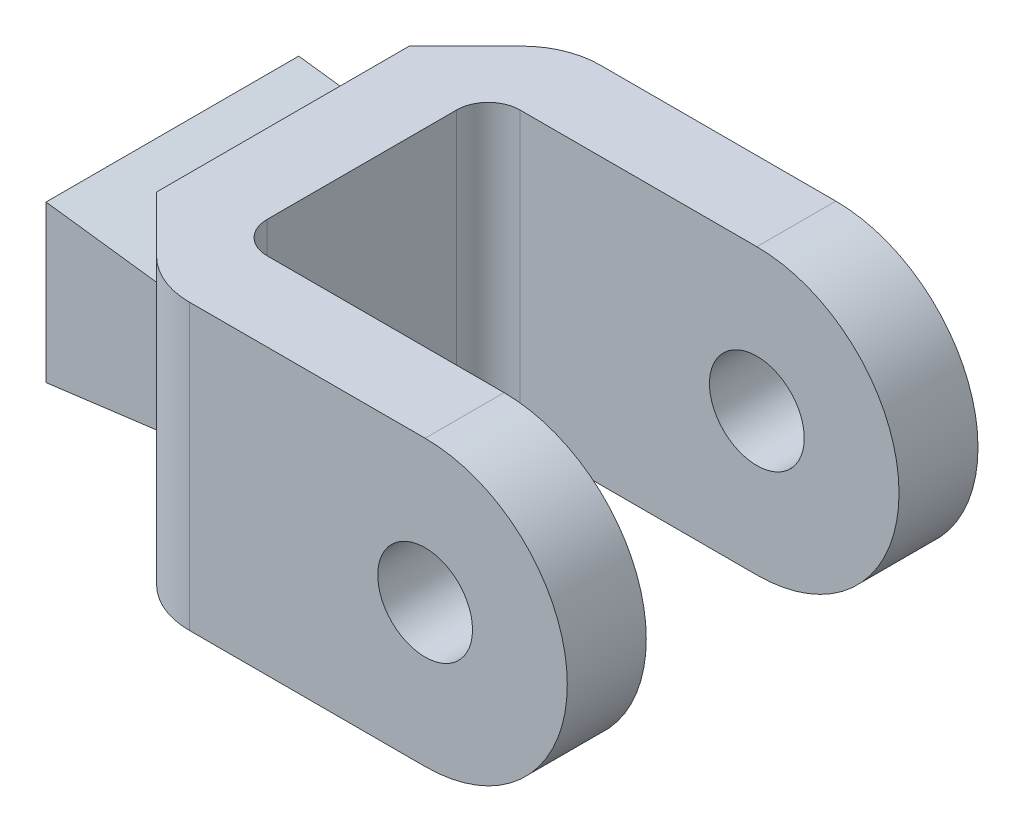
SolidWorks part; units mm, degrees
ref_plane "Front Plane" through (0, 0, 0) normal (0, 0, 1) x (1, 0, 0)
ref_plane "Top Plane" through (0, 0, 0) normal (0, 1, 0) x (1, 0, 0)
ref_plane "Right Plane" through (0, 0, 0) normal (1, 0, 0) x (0, 0, -1)
sketch "Sketch1" plane through (0, 0, 0) normal (0, 0, 1) x (1, 0, 0)
  line L0 (-2.2687, 0) -> (4.5375, 0) construction
  line L4 (-1.75, -2.475) -> (-1.75, 2.475)
  line L5 (1.4583, -2.0625) -> (-1.75, 2.475) construction
  line L6 (1.4583, 2.0625) -> (-1.75, -2.475) construction
  line L7 (-1.75, -2.475) -> (1.75, -2.025)
  line L8 (-1.75, 2.475) -> (1.75, 2.025)
  line L21 (1.75, 2.025) -> (1.75, 4.5)
  line L22 (4.25, -4.5) -> (1.75, -4.5)
  line L25 (4.25, -4.5) -> (4.25, 4.5)
  line L26 (4.25, 4.5) -> (1.75, 4.5)
  line L27 (1.75, -4.5) -> (1.75, -2.025)
  line L28 (4.25, -4.5) -> (1.75, 4.5) construction
  line L29 (4.25, 4.5) -> (1.75, -4.5) construction
  point P0 (0, 0)
  point P2 (3, 0)
  point P3 (3, 0)
  point P6 (1.75, 2.025)
  point P9 (1.75, -2.025)
  dimension "D1" = 4.95
  dimension "D2" = 2.5
  dimension "D3" = 9
extrude "Boss-Extrude1" add sketch "Sketch1" along normal blind 8 contours L8 L21 L26 L25 L22 L27 L7 L4
sketch "Sketch2" plane through (0, 0, 0) normal (0, 0, 1) x (1, 0, 0)
  line L0 (-1.75, 0) -> (25.7432, 0) construction
  line L1 (-1.75, -2.475) -> (-1.75, 2.475) construction
  line L3 (12.75, -4.5) -> (1.75, -4.5)
  line L5 (12.75, 4.5) -> (1.75, 4.5)
  line L6 (1.75, -4.5) -> (1.75, 4.5)
  line L7 (15.7356, -3.3669) -> (1.75, 4.5) construction
  line L8 (15.7356, 3.3669) -> (1.75, -4.5) construction
  line L11 (1.75, -4.5) -> (1.75, -2.025) construction
  arc A0 (12.75, -4.5) -> (12.75, 4.5) centre (12.75, 0) ccw
  circle A1 centre (12.75, 0) radius 1.5
  circle A2 centre (12.75, 0) radius 7.5 construction
  point P5 (9.75, 0)
  point P7 (17.25, 0)
  dimension "D3" = 3
  dimension "D4" = 15
  dimension "D1" = 15.5
  dimension "D2" = 9
extrude "Boss-Extrude3" add sketch "Sketch2" against normal blind 2.5
sketch "Sketch5" plane through (0, 0, 0) normal (0, 1, 0) x (1, 0, 0)
  line L0 (4.25, 0) -> (4.25, 4.091) construction
  line L1 (12.75, 2.5) -> (1.75, 2.5) construction
  line L2 (1.75, 0) -> (4.25, 2.5)
  line L3 (4.25, 2.5) -> (1.75, 2.5)
  line L4 (1.75, 2.5) -> (1.75, 0)
  point P3 (4.25, 2.5)
extrude "Cut-Extrude2" cut sketch "Sketch5" against normal through all and the other way through all
fillet "Fillet5" radius 1 1 edges at (4.25, 0, 0)
fillet "Fillet6" radius 2.5 1 edges at (4.25, 0, -2.5)
ref_plane "Plane1" through (0, 0, 4) normal (0, 0, -1) x (-1, 0, 0)
mirror "Mirror2" about plane through (0, 0, 4) normal (0, 0, -1) of "Cut-Extrude2", "Fillet6", "Fillet5", "Boss-Extrude3"
